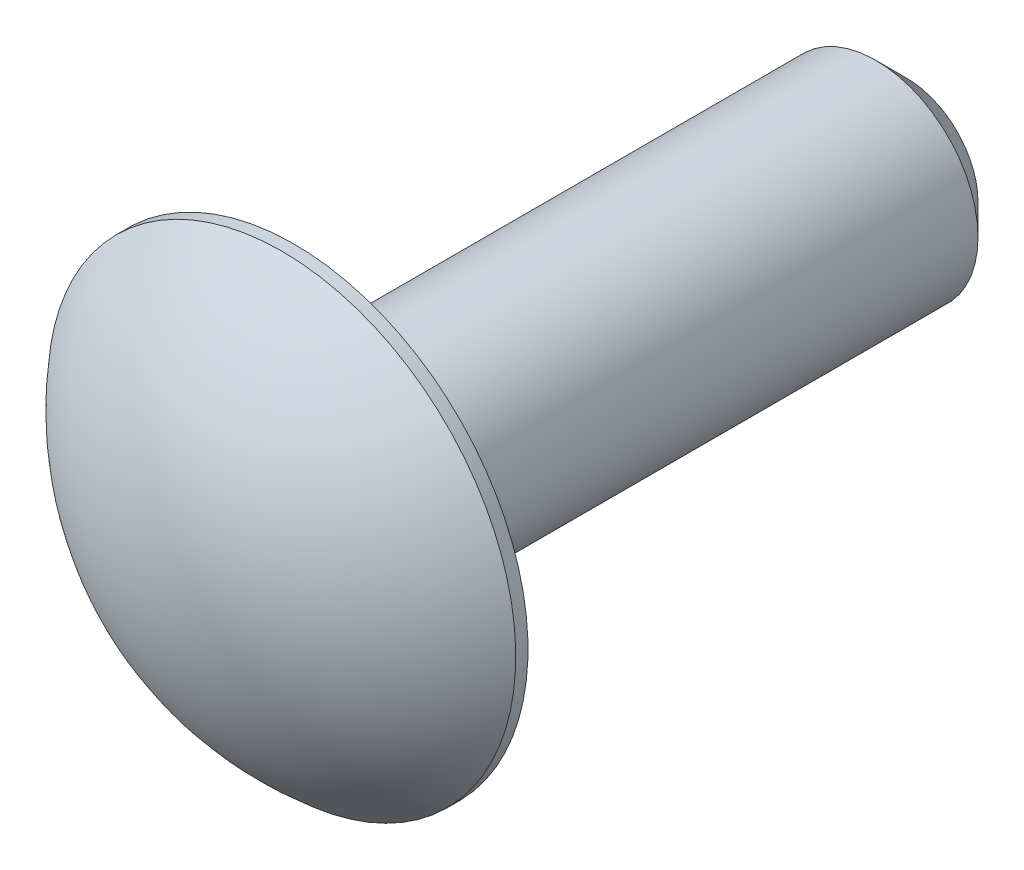
SolidWorks part; units mm, degrees
ref_plane "Front" through (0, 0, 0) normal (0, 0, 1) x (1, 0, 0)
ref_plane "Top" through (0, 0, 0) normal (0, 1, 0) x (1, 0, 0)
ref_plane "Right" through (0, 0, 0) normal (1, 0, 0) x (0, 0, -1)
sketch "Sketch1" plane through (0, 0, 0) normal (0, 0, 1) x (1, 0, 0)
  circle A0 centre (0, 0) radius 7.2771
  dimension "Head Dia" = 14.5542
extrude "Extrude3" add sketch "Sketch1" along normal blind 3.81
sketch "Sketch11" plane through (0, 0, 0) normal (1, 0, 0) x (0, 0, -1)
  line L0 (0, 0) -> (-4.064, 0) construction
  line L4 (-3.81, 7.2771) -> (-3.81, -7.2771) construction
  line L5 (-4.064, 8.7325) -> (0, 8.7325)
  line L7 (0, 8.7325) -> (0, 7.2771)
  line L8 (-0.381, 7.2771) -> (0, 7.2771)
  line L9 (0, -7.2771) -> (0, 7.2771) construction
  line L11 (0, 7.2771) -> (-3.81, 7.2771) construction
  line L13 (-3.81, 0) -> (-4.064, 0)
  line L14 (-4.064, 0) -> (-4.064, 8.7325)
  arc A0 (-0.381, 7.2771) -> (-3.81, 0) centre (5.6263, 0) ccw
  dimension "D3" = 0.254
  dimension "D1" = 0.381
  dimension "D5" = 1.4554
revolve "Cut-Revolve3" cut sketch "Sketch11" angle 360 about L0
sketch "Sketch4" plane through (0, 0, 0) normal (1, 0, 0) x (0, 0, -1)
  line L0 (0, 0) -> (19.05, 0)
  line L3 (19.05, 0) -> (19.05, 3.175)
  line L4 (19.05, 3.175) -> (0, 3.175)
  line L6 (0, 3.175) -> (0, 0)
  line L9 (19.05, 3.175) -> (19.05, -3.175) construction
  dimension "length" = 19.05
  dimension "dia" = 6.35
revolve "Revolve1" add sketch "Sketch4" angle 360 about L0
sketch "Sketch13" plane through (0, 0, -19.05) normal (0, 0, -1) x (-1, 0, 0)
  circle A2 centre (0, 0) radius 3.175
curve "Helix/Spiral1" pitch 1.27 height 22.86 turns 18
chamfer "Chamfer2" distance 0.9525 angle 45 1 edges at (3.175, 0, -19.05)
sketch "Sketch14" plane through (0, 0, 0) normal (1, 0, 0) x (0, 0, -1)
  line L0 (19.05, 3.2147) -> (20.1613, 3.2147)
  line L1 (20.1613, 3.2147) -> (19.685, 2.3555)
  line L2 (19.685, 2.3555) -> (19.5263, 2.3555)
  line L3 (19.5263, 2.3555) -> (19.05, 3.2147)
  line L4 (19.2881, 2.7851) -> (19.9231, 2.7851) construction
  dimension "D1" = 0.1588
  dimension "D2" = 58
  dimension "D3" = 0.635
  dimension "D4" = 0.0397
sweep "Cut-Sweep1" [suppressed] cut profiles "Sketch14" path "Helix/Spiral1"
ref_plane "Plane1" through (0, 0, 19.05) normal (0, 0, -1) x (-1, 0, 0)
sketch "Sketch29" [suppressed] plane through (0, 0, 28.575) normal (0, 0, -1) x (-1, 0, 0)
  circle A0 centre (0, 0) radius 1.7526 construction
  circle A1 centre (0, 0) radius 1.7526
  point P3 (0, -1.7526)
  point P4 (0, 1.7526)
extrude "Extrude11" [suppressed] add sketch "Sketch29" against normal up to surface (28.575 mm away)
ref_plane "Plane2" through (0, 0, 3.81) normal (0, 0, 1) x (1, 0, 0)
sketch "Sketch26" plane through (0, 0, 0) normal (0, 0, 1) x (1, 0, 0)
  circle A1 centre (0, 0) radius 0.5461
  dimension "D1" = 1.0922
extrude "Extrude13" add sketch "Sketch26" along normal up to surface (3.7942 mm away)
sketch "Sketch31" plane through (0, 0, 3.81) normal (0, 0, 1) x (1, 0, 0)
  line L0 (0.762, 3.4084) -> (0.762, 1.7462)
  line L1 (0.762, 1.7462) -> (1.7463, 0.762) construction
  line L2 (1.7463, 0.762) -> (3.4084, 0.762)
  line L3 (0, 3.4925) -> (0, 0)
  line L4 (0, 0) -> (3.4925, 0)
  line L5 (0, 0) -> (1.2541, 1.2541) construction
  line L6 (-0.762, 1.7462) -> (0.762, 1.7462) construction
  line L7 (0.762, 1.7462) -> (1.0503, 1.0503)
  line L8 (1.7463, 0.762) -> (1.0503, 1.0503)
  line L10 (-0.762, 3.4084) -> (-0.762, 1.7462) construction
  line L11 (-3.4925, 0) -> (0, 0) construction
  line L12 (1.7463, 0.762) -> (1.7463, 0) construction
  arc A0 (3.4925, 0) -> (3.4084, 0.762) centre (0, 0) ccw
  arc A1 (0.762, 3.4084) -> (0, 3.4925) centre (0, 0) ccw
  circle A2 centre (0, 0) radius 3.4925 construction
  point P2 (0, 1.7462)
  dimension "slot dia" = 6.985
  dimension "D1" = 45
  dimension "D2" = 22.5
  dimension "slot width" = 1.524
extrude "Extrude15" [suppressed] cut sketch "Sketch31" against normal blind 3.2385
draft "Draft1" [suppressed] type of draft neutral plane draft angle 15 neutral plane "Plane2" faces to draft 2 parameters "D1"=15
draft "Draft2" [suppressed] type of draft neutral plane draft angle 5 neutral plane "Plane2" faces to draft 4 parameters "D1"=5
pattern_circular "CirPattern1" [suppressed] count 4 over 360 of bodies 172
sketch "Sketch18" plane through (0, 0, 0) normal (1, 0, 0) x (0, 0, -1)
  line L1 (19.05, 3.175) -> (0, 3.175) construction
  point P0 (17.145, -3.175)
  point P1 (17.78, 3.175)
  point P2 (-3.81, 1.2541)
  dimension "D1" = 1.27
  dimension "D2" = 1.905
equation "\"D3@Helix/Spiral1\" = \"length@Sketch4\" + \"Head Ht@Extrude3\""
equation "\"D1@Sketch14\" = \"D4@Helix/Spiral1\" * .125"
equation "\"D3@Sketch14\" = \"D4@Helix/Spiral1\" * .5"
equation "\"D1@Sketch11\" = \"Head Ht@Extrude3\" / 10"
equation "\"D5@Sketch11\" = \"Head Dia@Sketch1\" / 10"
equation "\"D4@Sketch14\" = \"D1@Sketch14\" * .25"
equation "\"D1@Chamfer2\" = \"D4@Helix/Spiral1\" * .75"
equation "\"D1@Sketch18\" = \"D4@Helix/Spiral1\""
equation "\"D2@Sketch18\" = \"D4@Helix/Spiral1\" * 1.5"
equation "\"D1@Extrude15\" = \"Head Ht@Extrude3\" * .85"
